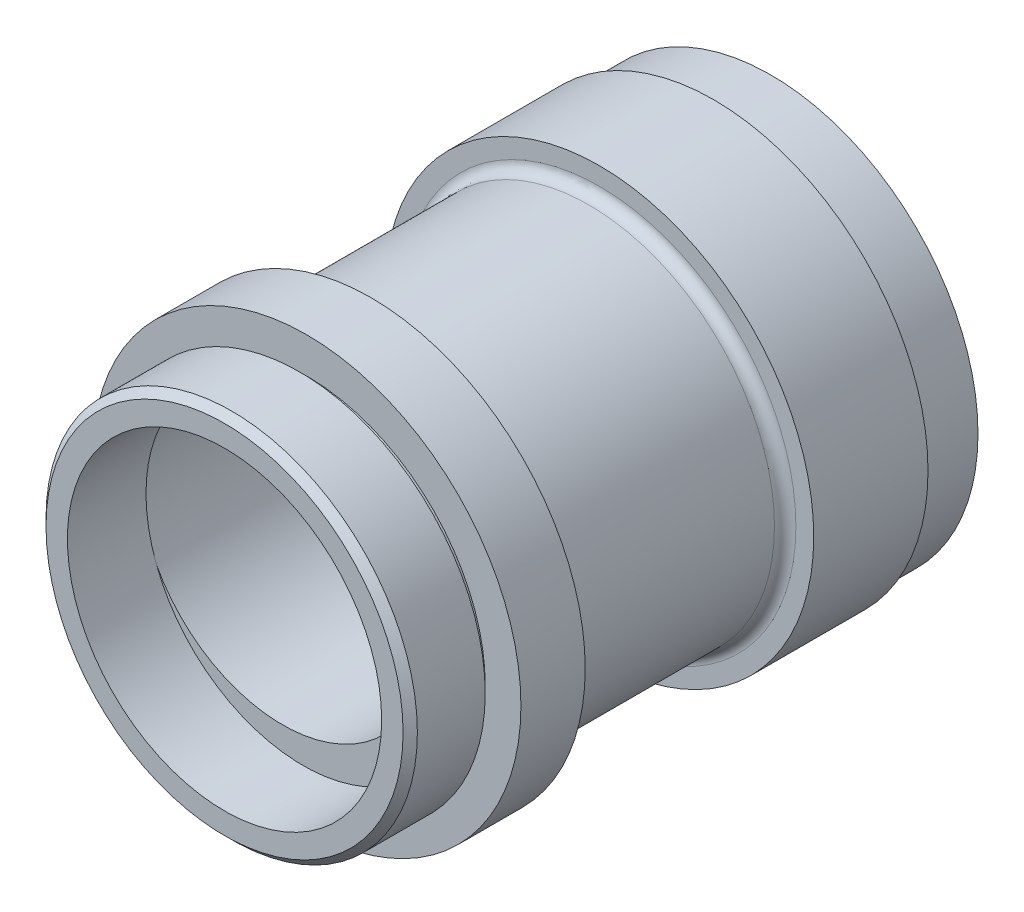
SolidWorks part; units mm, degrees
ref_plane "Plan de face" through (0, 0, 0) normal (0, 0, 1) x (1, 0, 0)
ref_plane "Plan de dessus" through (0, 0, 0) normal (0, 1, 0) x (1, 0, 0)
ref_plane "Plan de droite" through (0, 0, 0) normal (1, 0, 0) x (0, 0, -1)
sketch "Sketch1" plane through (0, 0, 0) normal (0, 0, 1) x (1, 0, 0)
  circle A0 centre (0, 0) radius 14.5
  dimension "D1" = 29
extrude "Boss-Extrude1" add sketch "Sketch1" along normal blind 4
sketch "Sketch2" plane through (0, 0, 4) normal (0, 0, 1) x (1, 0, 0)
  circle A0 centre (0, 0) radius 15
  dimension "D1" = 30
extrude "Boss-Extrude2" add sketch "Sketch2" along normal blind 8
sketch "Sketch3" plane through (0, 0, 12) normal (0, 0, 1) x (1, 0, 0)
  circle A0 centre (0, 0) radius 13
  dimension "D1" = 26
extrude "Boss-Extrude3" add sketch "Sketch3" along normal blind 16
sketch "Sketch4" plane through (0, 0, 28) normal (0, 0, 1) x (1, 0, 0)
  circle A0 centre (0, 0) radius 15
  dimension "D1" = 30
extrude "Boss-Extrude4" add sketch "Sketch4" along normal blind 4.5
sketch "Sketch5" plane through (0, 0, 32.5) normal (0, 0, 1) x (1, 0, 0)
  circle A0 centre (0, 0) radius 12.5
  dimension "D1" = 25
extrude "Boss-Extrude5" add sketch "Sketch5" along normal blind 0.5
sketch "Sketch6" plane through (0, 0, 33) normal (0, 0, 1) x (1, 0, 0)
  circle A0 centre (0, 0) radius 13
  dimension "D1" = 26
extrude "Boss-Extrude6" add sketch "Sketch6" along normal blind 5.25
cosmetic thread "Cosmetic Thread1" parameters "D2"=25
sketch "Sketch7" plane through (0, 0, 38.25) normal (0, 0, 1) x (1, 0, 0)
  circle A0 centre (0, 0) radius 11
  dimension "D1" = 22
extrude "Cut-Extrude1" cut sketch "Sketch7" against normal blind 5.5
sketch "Sketch8" plane through (0, 0, 32.75) normal (0, 0, 1) x (1, 0, 0)
  circle A0 centre (-1.44, 0.75) radius 10
  circle A1 centre (0, 0) radius 15 construction
  dimension "D1" = 20
  dimension "D2" = 0.75
  dimension "D3" = 1.44
other "AlignGroup1"
extrude "Cut-Extrude2" cut sketch "Sketch8" against normal blind 32.75 contours A0
fillet "Fillet1" radius 0.75 2 edges at (13, 0, 12) (13, 0, 28)
chamfer "Chamfer1" distance 0.5 angle 45 1 edges at (13, 0, 38.25)
sketch "Sketch14" plane through (0, 0, 0) normal (0, 0, -1) x (-1, 0, 0)
  circle A0 centre (-9.5, 8.9) radius 1
  point P0 (-9.5, 8.9)
  dimension "D1" = 9.5
  dimension "D4" = 2
  dimension "D2" = 8.9
hole_wizard "Ø2.0 (2) Diameter Hole3" positions "Sketch14" profile "Sketch15" hole size "Ø2.0" standard "ISO"
sketch "Sketch15" plane through (9.5, 8.9, 0) normal (1, 0, 0) x (0, 1, 0)
  line L0 (0, 0) -> (0, 9.25)
  line L1 (0, 9.25) -> (1, 8.6491)
  line L2 (1, 8.6491) -> (1, 0)
  line L5 (1, 0) -> (0, 0)
  line L10 (0, 9.25) -> (-1, 8.6491) construction
  line L11 (0, -6.35) -> (0, 107.95) construction
  dimension "Hole Dia." = 2
  dimension "Hole Depth" = 9.25
  dimension "Drill Angle" = 118
